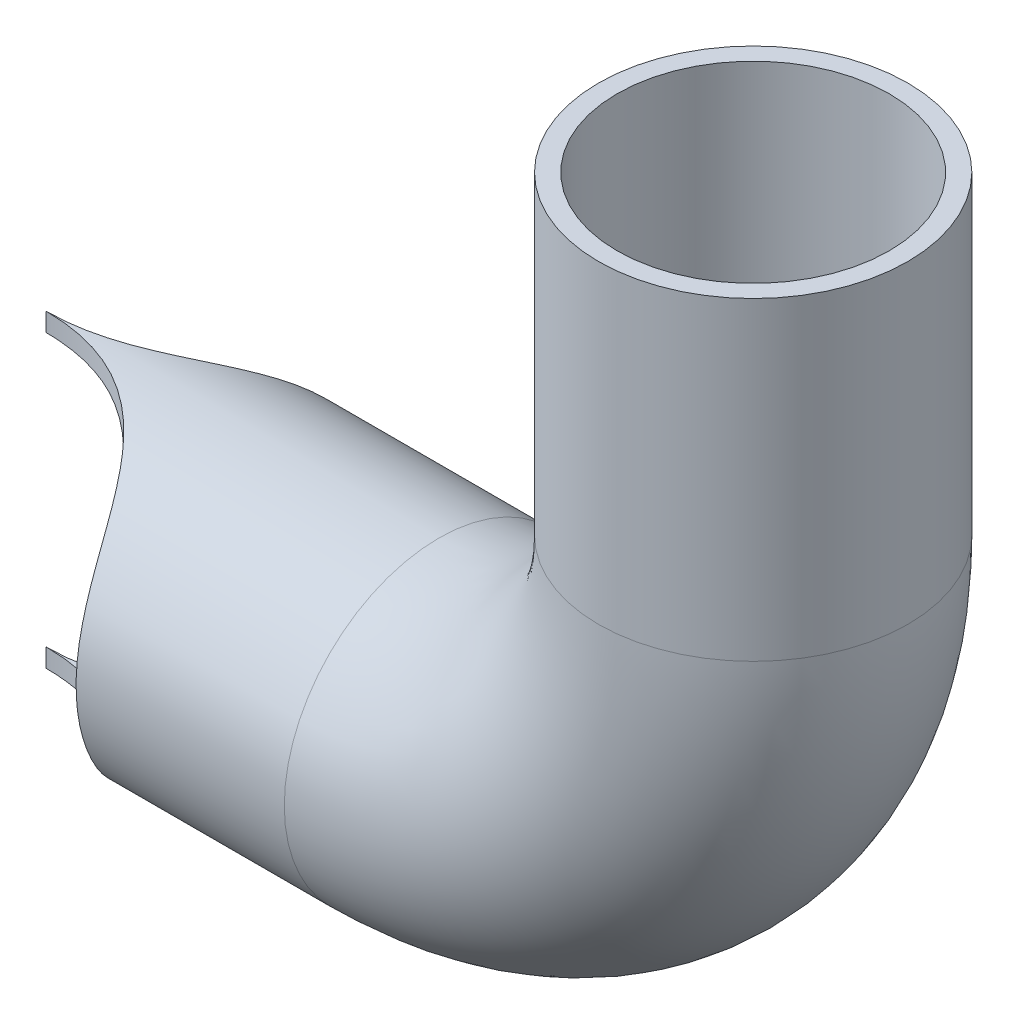
SolidWorks part; units mm, degrees
ref_plane "Front Plane" through (0, 0, 0) normal (0, 0, 1) x (1, 0, 0)
ref_plane "Top Plane" through (0, 0, 0) normal (0, 1, 0) x (1, 0, 0)
ref_plane "Right Plane" through (0, 0, 0) normal (1, 0, 0) x (0, 0, -1)
sketch "Sketch1" plane through (0, 0, 0) normal (1, 0, 0) x (0, 0, -1)
  circle A0 centre (0, 0) radius 12.5
  dimension "D1" = 25
sketch "Sketch2" plane through (0, 0, 0) normal (0, 0, 1) x (1, 0, 0)
  line L0 (0, 0) -> (31.75, 0)
  line L1 (57.15, 25.4) -> (57.15, 50.8)
  arc A0 (31.75, 0) -> (57.15, 25.4) centre (31.75, 25.4) ccw
  dimension "D1" = 50.8
  dimension "D2" = 31.75
  dimension "D3" = 25.4
sweep "Sweep1" add profiles "Sketch1" path "Sketch2"
sketch "Sketch3" plane through (0, 0, 0) normal (-1, 0, 0) x (0, 0, 1)
  circle A0 centre (0, 0) radius 11
  dimension "D1" = 22
sweep "Cut-Sweep1" cut profiles "Sketch3" path "Sketch2<2>"
sketch "Sketch2<2>" plane through (0, 0, 0) normal (0, 0, 1) x (1, 0, 0) same geometry as "Sketch2"
sketch "Sketch6" plane through (0, 0, 0) normal (-1, 0, 0) x (0, 0, 1)
  line L0 (0, 0) -> (0, 25.4) construction
  point P0 (0, 12.7)
  point P1 (0, 0)
ref_plane "Plane1" through (0, 12.7, 0) normal (0, 1, 0) x (1, 0, 0)
sketch "Sketch7" plane through (0, 12.7, 0) normal (0, 1, 0) x (1, 0, 0)
  line L0 (0, -12.5) -> (0, 12.5) construction
  circle A0 centre (0, 15.1576) radius 15.1576
  point P2 (0, 7.0861)
  point P5 (0, 17.5191)
  dimension "D1" = 30.3152
extrude "Cut-Extrude1" cut sketch "Sketch7" against normal through all contours A0
mirror "Mirror1" about plane through (0, 0, 0) normal (0, 0, 1) of "Cut-Extrude1"
